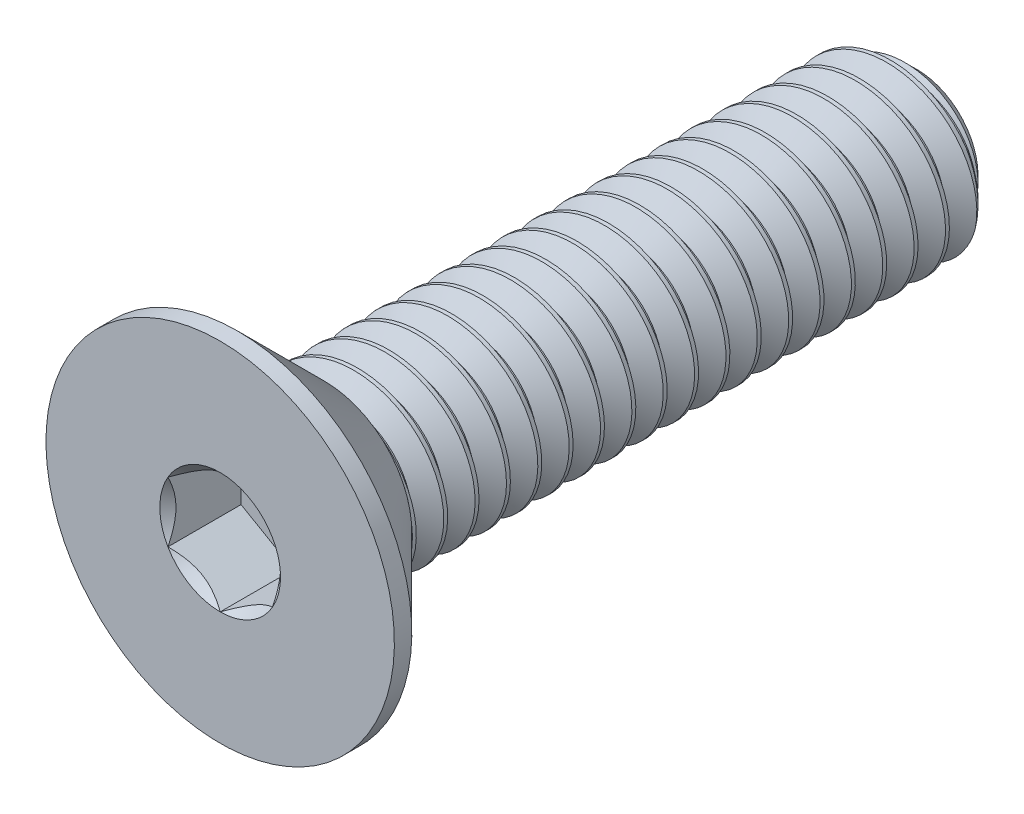
SolidWorks part; units mm, degrees
ref_plane "Front" through (0, 0, 0) normal (0, 0, 1) x (1, 0, 0)
ref_plane "Top" through (0, 0, 0) normal (0, 1, 0) x (1, 0, 0)
ref_plane "Right" through (0, 0, 0) normal (1, 0, 0) x (0, 0, -1)
sketch "Sketch1" plane through (0, 0, 0) normal (1, 0, 0) x (0, 0, -1)
  line L0 (-5, 2.5) -> (-4.75, 2.5) construction
  line L1 (-4.75, 2.5) -> (-3.5, 1.25) construction
  line L2 (-5, 1.25) -> (5, 1.25) construction
  line L3 (5, 1.25) -> (5, 0) construction
  line L4 (5, 0) -> (-5, 0) construction
  line L5 (-5, 0) -> (-5, 2.5) construction
  line L6 (-5, 2.5) -> (-5, -2.5) construction
  line L7 (5, 1.25) -> (5, -1.25) construction
  line L8 (-5, -2.5) -> (-4.75, -2.5) construction
  line L9 (-4.75, -2.5) -> (-3.5, -1.25) construction
  line L11 (-5, 1.25) -> (-5, 0) construction
  line L12 (-3.5, 1.25) -> (-3.5, 0) construction
  line L13 (4.9719, 1.2987) -> (5.1969, 0.909) construction
  line L14 (5.1969, 0.909) -> (5.4219, 1.2987) construction
  line L15 (5.4219, 1.2987) -> (4.9719, 1.2987) construction
  line L16 (5.1969, 1.2987) -> (5.1969, 1.25) construction
  line L17 (5.1969, 1.25) -> (5.1969, 0.9577) construction
  line L18 (5.1969, 0.9577) -> (5.1969, 0.909) construction
  line L19 (5.1969, 1.2744) -> (5.4078, 1.2744) construction
  line L20 (5.1969, 1.2744) -> (4.9859, 1.2744) construction
  line L21 (5, 1.25) -> (5.3938, 1.25) construction
  line L22 (5.1688, 0.9577) -> (5.225, 0.9577) construction
  line L23 (5, -1.25) -> (-3.5, -1.25) construction
  point P10 (3.875, -1.25)
  point P24 (-3.5, 1.25)
  point P30 (0, 0)
  dimension "Head Diameter" = 5
  dimension "Head Height" = 1.5
  dimension "Length" = 10
  dimension "Countersink Angle" = 90
  dimension "Thread Pitch" = 0.45
  dimension "D2" = 0.0563
  dimension "Minimum Thread Length" = 8.5
  dimension "Thread Size" = 2.5
  dimension "D1" = 1.125
sketch "Sketch2" plane through (0, 0, 0) normal (0, 0, 1) x (1, 0, 0)
  line L1 (0, 0.866) -> (-0.75, 0.433) construction
  line L2 (-0.75, 0.433) -> (-0.75, -0.433) construction
  line L3 (-0.75, -0.433) -> (0, -0.866) construction
  line L4 (0, -0.866) -> (0.75, -0.433) construction
  line L5 (0.75, -0.433) -> (0.75, 0.433) construction
  line L6 (0.75, 0.433) -> (0, 0.866) construction
  circle A0 centre (0, 0) radius 0.75 construction
  dimension "Drive Size" = 1.5
sketch "Sketch3" plane through (0, 0, 0) normal (1, 0, 0) x (0, 0, -1)
  line L0 (-5, 1.25) -> (5, 1.25)
  line L1 (5, 1.25) -> (5, 0)
  line L2 (5, 0) -> (-5, 0)
  line L3 (-5, 0) -> (-5, 1.25)
revolve "Revolve1" add sketch "Sketch3" angle 360 about L4
chamfer "Chamfer1" distance 0.375 angle 45 1 edges at (0, 1.25, -5)
sketch "Sketch6" plane through (0, 0, 0) normal (1, 0, 0) x (0, 0, -1)
  line L0 (-5, 2.5) -> (-4.75, 2.5)
  line L1 (-4.75, 2.5) -> (-3.5, 1.25)
  line L2 (-3.5, 1.25) -> (-3.5, 0)
  line L3 (-3.5, 0) -> (-5, 0)
  line L4 (-5, 0) -> (-5, 2.5)
revolve "Revolve2" add sketch "Sketch6" angle 360 about L4
sketch "Sketch8" plane through (0, 0, 5) normal (0, 0, 1) x (1, 0, 0)
  line L0 (0, 0.866) -> (-0.75, 0.433) construction
  line L1 (0.75, 0.433) -> (0, 0.866) construction
  line L2 (0.75, -0.433) -> (0.75, 0.433) construction
  line L3 (0, -0.866) -> (0.75, -0.433) construction
  line L4 (-0.75, 0.433) -> (-0.75, -0.433) construction
  line L5 (-0.75, -0.433) -> (0, -0.866) construction
  line L6 (0, 0.866) -> (-0.75, 0.433)
  line L7 (0.75, 0.433) -> (0, 0.866)
  line L8 (0.75, -0.433) -> (0.75, 0.433)
  line L9 (0, -0.866) -> (0.75, -0.433)
  line L10 (-0.75, 0.433) -> (-0.75, -0.433)
  line L11 (-0.75, -0.433) -> (0, -0.866)
extrude "Cut-Extrude1" cut sketch "Sketch8" against normal blind 1.05
sketch "Sketch9" plane through (0, 0, 5) normal (0, 0, 1) x (1, 0, 0)
  circle A0 centre (0, 0) radius 0.866
extrude "Cut-Extrude2" cut sketch "Sketch9" against normal up to next (1.05 mm away) draft 45
ref_plane "Plane1" through (0, 0, 3.5) normal (0, 0, 1) x (1, 0, 0)
split "Split1" trim tools "Plane1" bodies to split 124 resulting bodies 126 127
sketch "Sketch4" plane through (0, 0, -5) normal (0, 0, -1) x (-1, 0, 0)
  circle A0 centre (0, 0) radius 1.25 construction
  circle A1 centre (0, 0) radius 1.25
curve "Helix/Spiral1" pitch 0.45 height 8.95 radius 1.25 centre (0, 0, -5) axis (0, 0, 1) start towards (0, 1, 0)
sketch "Sketch10" plane through (0, 0, 0) normal (1, 0, 0) x (0, 0, -1)
  line L0 (4.9859, 1.2744) -> (5.4078, 1.2744)
  line L1 (5.4078, 1.2744) -> (5.225, 0.9577)
  line L2 (5.225, 0.9577) -> (5.1688, 0.9577)
  line L3 (5.1688, 0.9577) -> (4.9859, 1.2744)
sweep "Cut-Sweep1" cut profiles "Sketch10" path "Helix/Spiral1"
equation "\"D2@Sketch1\" = \"Thread Pitch@Sketch1\" / 8"
equation "\"D4@Helix/Spiral1\"=\"Thread Pitch@Sketch1\""
equation "\"D3@Helix/Spiral1\"=\"Minimum Thread Length@Sketch1\"+\"Thread Pitch@Sketch1\""
equation "\"D1@Chamfer1\"=\"Thread Size@Sketch1\"*.15"
equation "\"D1@Cut-Extrude1\"=\"Head Height@Sketch1\"*.7"
equation "\"D1@Sketch1\"=\"Thread Pitch@Sketch1\"*2.5"
